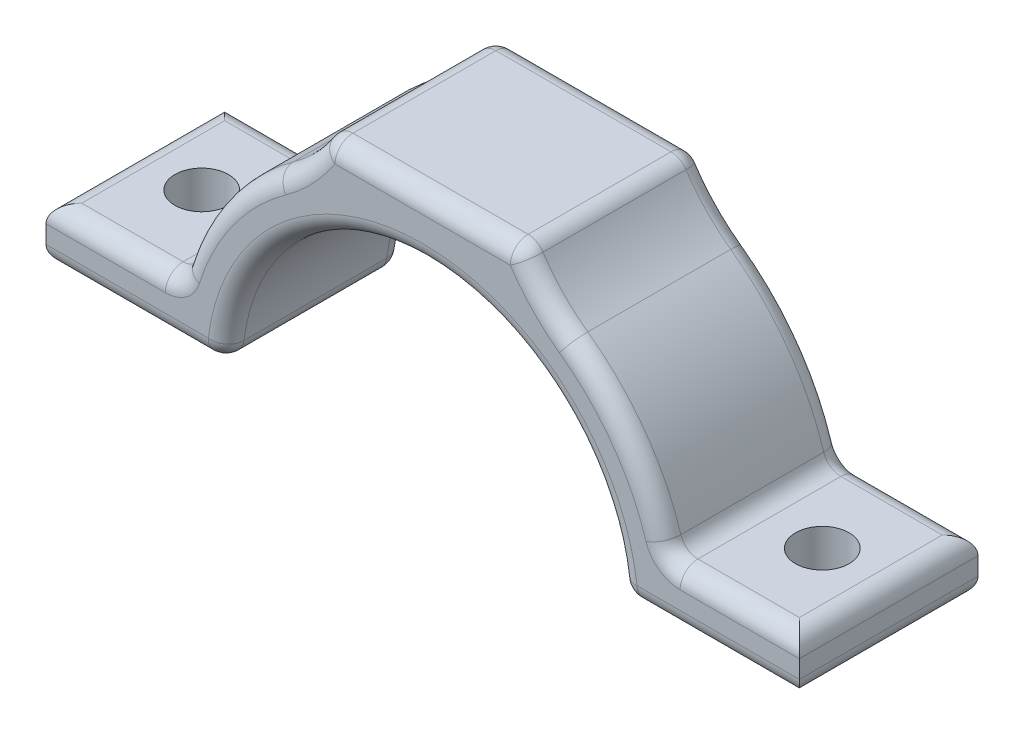
SolidWorks part; units mm, degrees
ref_plane "Front Plane" through (0, 0, 0) normal (0, 0, 1) x (1, 0, 0)
ref_plane "Top Plane" through (0, 0, 0) normal (0, 1, 0) x (1, 0, 0)
ref_plane "Right Plane" through (0, 0, 0) normal (1, 0, 0) x (0, 0, -1)
sketch "Sketch1" plane through (0, 0, 0) normal (0, 0, 1) x (1, 0, 0)
  line L0 (-14.1, 0) -> (14.1, 0) construction
  line L2 (-5.4599, 13) -> (-5.4599, 14.5)
  line L3 (-5.4599, 14.5) -> (5.4599, 14.5)
  line L4 (5.4599, 14.5) -> (5.4599, 13)
  line L5 (-21.0881, 0.5133) -> (-11.0881, 0.5133)
  line L6 (-21.0881, 0.5133) -> (-21.0881, 3.5133)
  line L7 (-21.0881, 3.5133) -> (-13.6553, 3.5133)
  line L8 (0, 0) -> (0, 11.1) construction
  line L9 (21.0881, 0.5133) -> (11.0881, 0.5133)
  line L10 (21.0881, 0.5133) -> (21.0881, 3.5133)
  line L11 (21.0881, 3.5133) -> (13.6553, 3.5133)
  arc A0 (11.0881, 0.5133) -> (-11.0881, 0.5133) centre (0, 0) ccw
  arc A1 (13.6553, 3.5133) -> (5.4599, 13) centre (0, 0) ccw
  arc A2 (-5.4599, 13) -> (-13.6553, 3.5133) centre (0, 0) ccw
  dimension "D1" = 22.2
  dimension "D2" = 3
  dimension "D3" = 1.5
  dimension "D5" = 3
  dimension "D6" = 10
extrude "Boss-Extrude1" add sketch "Sketch1" along normal blind 10
sketch "Sketch2" plane through (0, 3.5133, 0) normal (0, 1, 0) x (1, 0, 0)
  line L0 (21.0881, 0) -> (13.6553, 0) construction
  line L1 (-13.6553, 0) -> (-21.0881, 0) construction
  line L2 (-21.0881, -10) -> (-21.0881, 0) construction
  line L3 (21.0881, -10) -> (21.0881, 0) construction
  circle A0 centre (-17.3717, -5) radius 1.5
  circle A1 centre (17.3717, -5) radius 1.5
  point P6 (17.3717, 0)
  point P7 (0, 0)
  point P10 (-17.3717, 0)
  point P11 (0, 0)
  point P14 (-21.0881, -5)
  point P15 (0, 0)
  point P18 (21.0881, -5)
  dimension "D1" = 3
extrude "Cut-Extrude1" cut sketch "Sketch2" against normal up to next
fillet "Fillet1" radius 10 2 edges at (5.4599, 13, 5) (-5.4599, 13, 5)
fillet "Fillet2" radius 1 30 edges at (-17.3717, 3.5133, 10) (-17.3717, 3.5133, 0) (17.3717, 3.5133, 10) (17.3717, 3.5133, 0) (-6.6916, 12.8241, 0) (-6.6916, 12.8241, 10) (6.6916, 12.8241, 10) (6.6916, 12.8241, 0) (-13.6553, 3.5133, 5) (-11.6444, 7.9509, 0) (-11.6444, 7.9509, 10) (-11.0881, 0.5133, 5) (0, 11.1, 10) (11.0881, 0.5133, 5) (0, 11.1, 0) (13.6553, 3.5133, 5) (11.6444, 7.9509, 10) (11.6444, 7.9509, 0) (5.4599, 14.5, 5) (0, 14.5, 10) (-5.4599, 14.5, 5) (0, 14.5, 0) (-16.0881, 0.5133, 10) (-21.0881, 0.5133, 5) (-16.0881, 0.5133, 0) (16.0881, 0.5133, 10) (16.0881, 0.5133, 0) (-21.0881, 3.5133, 5) (21.0881, 0.5133, 5) (21.0881, 3.5133, 5)
